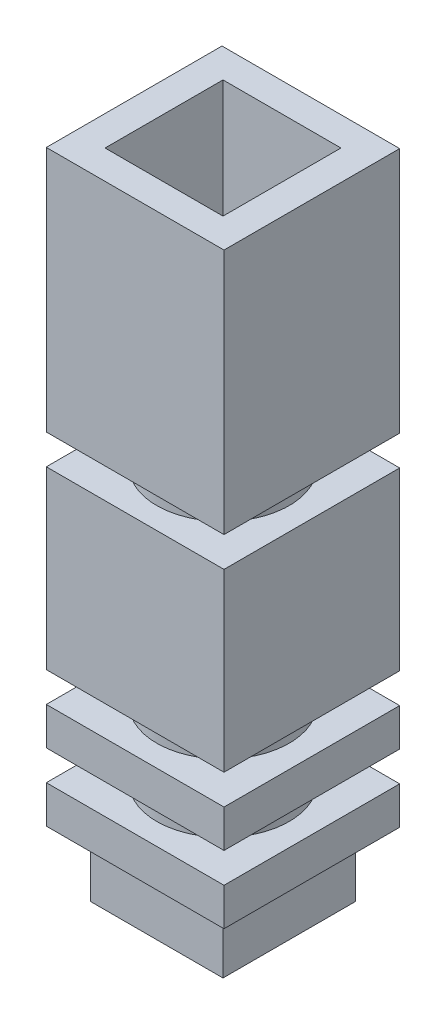
SolidWorks part; units mm, degrees
ref_plane "Front Plane" through (0, 0, 0) normal (0, 0, 1) x (1, 0, 0)
ref_plane "Top Plane" through (0, 0, 0) normal (0, 1, 0) x (1, 0, 0)
ref_plane "Right Plane" through (0, 0, 0) normal (1, 0, 0) x (0, 0, -1)
sketch "Sketch1" plane through (0, 0, 0) normal (0, 0, 1) x (1, 0, 0)
  line L0 (4.4958, 14.5796) -> (-4.4958, 14.5796) construction
  line L1 (-4.4958, 19.0246) -> (4.4958, 19.0246)
  line L2 (-4.4958, 19.0246) -> (-4.4958, 10.1346)
  line L3 (-4.4958, 10.1346) -> (4.4958, 10.1346)
  line L4 (4.4958, 19.0246) -> (4.4958, 10.1346)
  line L5 (-4.4958, 19.0246) -> (4.4958, 10.1346) construction
  line L6 (-4.4958, 10.1346) -> (4.4958, 19.0246) construction
  line L7 (-4.4958, 8.6106) -> (4.4958, 8.6106)
  line L8 (-4.4958, 8.6106) -> (-4.4958, 6.7056)
  line L9 (-4.4958, 6.7056) -> (4.4958, 6.7056)
  line L10 (4.4958, 8.6106) -> (4.4958, 6.7056)
  line L11 (-4.4958, 8.6106) -> (4.4958, 6.7056) construction
  line L12 (-4.4958, 6.7056) -> (4.4958, 8.6106) construction
  line L13 (-4.4958, 5.1816) -> (4.4958, 5.1816)
  line L14 (-4.4958, 5.1816) -> (-4.4958, 3.2766)
  line L15 (-4.4958, 3.2766) -> (4.4958, 3.2766)
  line L16 (4.4958, 5.1816) -> (4.4958, 3.2766)
  line L17 (-4.4958, 5.1816) -> (4.4958, 3.2766) construction
  line L18 (-4.4958, 3.2766) -> (4.4958, 5.1816) construction
  line L19 (-4.4958, 33.02) -> (4.4958, 33.02)
  line L20 (-4.4958, 33.02) -> (-4.4958, 20.5486)
  line L21 (-4.4958, 20.5486) -> (4.4958, 20.5486)
  line L22 (4.4958, 33.02) -> (4.4958, 20.5486)
  line L23 (-4.4958, 33.02) -> (4.4958, 20.5486) construction
  line L24 (-4.4958, 20.5486) -> (4.4958, 33.02) construction
  line L25 (-3.3528, 3.2766) -> (3.3528, 3.2766)
  line L26 (-3.3528, 3.2766) -> (-3.3528, 0)
  line L27 (-3.3528, 0) -> (3.3528, 0)
  line L28 (3.3528, 3.2766) -> (3.3528, 0)
  line L29 (-3.3528, 3.2766) -> (3.3528, 0) construction
  line L30 (-3.3528, 0) -> (3.3528, 3.2766) construction
  line L31 (4.4958, 7.6581) -> (-4.4958, 7.6581) construction
  line L32 (4.4958, 4.2291) -> (-4.4958, 4.2291) construction
  line L33 (3.3528, 1.6383) -> (-3.3528, 1.6383) construction
  line L34 (4.4958, 26.7843) -> (-4.4958, 26.7843) construction
  line L35 (-3.3528, 10.1346) -> (3.3528, 10.1346)
  line L36 (-3.3528, 10.1346) -> (-3.3528, 8.6106)
  line L37 (-3.3528, 8.6106) -> (3.3528, 8.6106)
  line L38 (3.3528, 10.1346) -> (3.3528, 8.6106) construction
  line L39 (-3.3528, 10.1346) -> (3.3528, 8.6106) construction
  line L40 (-3.3528, 8.6106) -> (3.3528, 10.1346) construction
  line L41 (-3.3528, 6.7056) -> (3.3528, 6.7056)
  line L42 (-3.3528, 6.7056) -> (-3.3528, 5.1816)
  line L43 (-3.3528, 5.1816) -> (3.3528, 5.1816)
  line L44 (3.3528, 6.7056) -> (3.3528, 5.1816) construction
  line L45 (-3.3528, 6.7056) -> (3.3528, 5.1816) construction
  line L46 (-3.3528, 5.1816) -> (3.3528, 6.7056) construction
  line L47 (-3.3528, 20.5486) -> (3.3528, 20.5486)
  line L48 (-3.3528, 20.5486) -> (-3.3528, 19.0246)
  line L49 (-3.3528, 19.0246) -> (3.3528, 19.0246)
  line L50 (3.3528, 20.5486) -> (3.3528, 19.0246) construction
  line L51 (-3.3528, 20.5486) -> (3.3528, 19.0246) construction
  line L52 (-3.3528, 19.0246) -> (3.3528, 20.5486) construction
  line L53 (0, 6.7056) -> (0, 5.1816)
  line L54 (0, 10.1346) -> (0, 8.6106)
  line L55 (0, 20.5486) -> (0, 19.0246)
  point P0 (0, 14.5796)
  point P5 (0, 7.6581)
  point P10 (0, 4.2291)
  point P15 (0, 26.7843)
  point P20 (0, 1.6383)
  point P33 (0, 5.9436)
  point P34 (0, 9.3726)
  point P46 (0, 19.7866)
  point P52 (0, 0)
  dimension "D1" = 6.7056
  dimension "D2" = 8.9916
  dimension "D3" = 1.905
  dimension "D4" = 8.89
  dimension "D5" = 12.4714
  dimension "D6" = 1.524
  dimension "D7" = 33.02
extrude "Boss-Extrude1" add sketch "Sketch1" along normal mid plane 8.89 contours L16 L13 L14 L15 region at (0, 4.2291, 0)
revolve "Revolve1" add sketch "Sketch1<4>" angle 360 about L53 region at (-1.6764, 5.9436, 0)
sketch "Sketch1<4>" plane through (0, 0, 0) normal (0, 0, 1) x (1, 0, 0) same geometry as "Sketch1"
extrude "Boss-Extrude2" add sketch "Sketch1<5>" along normal mid plane 8.89 contours L10 L7 L37 L8 L9 L41 region at (0, 7.6581, 0)
sketch "Sketch1<5>" plane through (0, 0, 0) normal (0, 0, 1) x (1, 0, 0) same geometry as "Sketch1"
revolve "Revolve2" add sketch "Sketch1<6>" angle 360 about L54 region at (-1.6764, 9.3726, 0)
sketch "Sketch1<6>" plane through (0, 0, 0) normal (0, 0, 1) x (1, 0, 0) same geometry as "Sketch1"
extrude "Boss-Extrude3" add sketch "Sketch1<7>" along normal mid plane 8.89 contours L4 L1 L49 L2 L3 L35 region at (0, 14.5796, 0)
sketch "Sketch1<7>" plane through (0, 0, 0) normal (0, 0, 1) x (1, 0, 0) same geometry as "Sketch1"
revolve "Revolve3" add sketch "Sketch1<8>" angle 360 about L55 region at (-1.6764, 19.7866, 0)
sketch "Sketch1<8>" plane through (0, 0, 0) normal (0, 0, 1) x (1, 0, 0) same geometry as "Sketch1"
extrude "Boss-Extrude4" add sketch "Sketch1<9>" along normal mid plane 8.89 contours L22 L19 L20 L21 L47 region at (0, 26.7843, 0)
sketch "Sketch1<9>" plane through (0, 0, 0) normal (0, 0, 1) x (1, 0, 0) same geometry as "Sketch1"
extrude "Boss-Extrude5" add sketch "Sketch1<10>" along normal mid plane 6.7056 contours L28 L15 L26 L27 region at (0, 1.6383, 0)
sketch "Sketch1<10>" plane through (0, 0, 0) normal (0, 0, 1) x (1, 0, 0) same geometry as "Sketch1"
sketch "Sketch2" plane through (0, 33.02, 0) normal (0, 1, 0) x (1, 0, 0)
  line L0 (2.9845, 2.9845) -> (2.9845, 4.445) construction
  line L1 (-2.9845, -2.9845) -> (2.9845, -2.9845)
  line L2 (-2.9845, -2.9845) -> (-2.9845, 2.9845)
  line L3 (-2.9845, 2.9845) -> (2.9845, 2.9845)
  line L4 (2.9845, -2.9845) -> (2.9845, 2.9845)
  line L5 (-2.9845, -2.9845) -> (2.9845, 2.9845) construction
  line L6 (-2.9845, 2.9845) -> (2.9845, -2.9845) construction
  line L7 (-4.4958, 4.445) -> (4.4958, 4.445) construction
  point P0 (0, 0)
  dimension "D1" = 5.969
extrude "Cut-Extrude1" cut sketch "Sketch2" against normal blind 11.0109
sketch "Sketch3" plane through (0, 0, 0) normal (0, -1, 0) x (-1, 0, 0)
  circle A0 centre (0, 0) radius 2.0574
  dimension "D1" = 4.1148
extrude "Cut-Extrude2" cut sketch "Sketch3" against normal up to next
